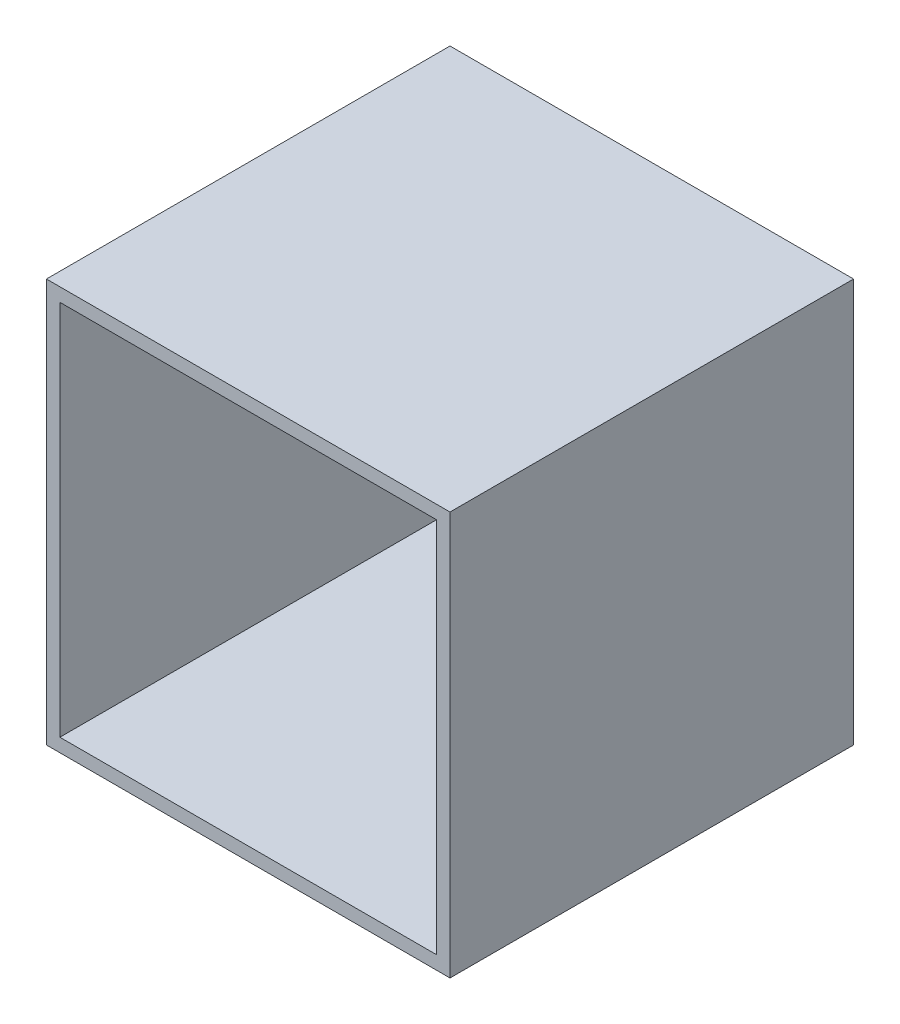
SolidWorks part; units mm, degrees
ref_plane "Front Plane" through (0, 0, 0) normal (0, 0, 1) x (1, 0, 0)
ref_plane "Top Plane" through (0, 0, 0) normal (0, 1, 0) x (1, 0, 0)
ref_plane "Right Plane" through (0, 0, 0) normal (1, 0, 0) x (0, 0, -1)
sketch "Sketch1" plane through (0, 0, 0) normal (0, 1, 0) x (1, 0, 0)
  line L1 (-38.1, -38.1) -> (38.1, -38.1)
  line L2 (-38.1, -38.1) -> (-38.1, 38.1)
  line L3 (-38.1, 38.1) -> (38.1, 38.1)
  line L4 (38.1, -38.1) -> (38.1, 38.1)
  line L5 (-38.1, -38.1) -> (38.1, 38.1) construction
  line L6 (-38.1, 38.1) -> (38.1, -38.1) construction
  point P0 (0, 0)
  dimension "D1" = 76.2
  dimension "D2" = 76.2
extrude "box" add sketch "Sketch1" along normal blind 76.2
shell "hollow it" thickness 2.54 removed face at (0, 38.1, 38.1)
sketch "Sketch2" plane through (0, 0, -38.1) normal (0, 0, -1) x (-1, 0, 0)
  line L0 (-38.1, 76.2) -> (38.1, 76.2) construction
  line L1 (-27.94, 69.85) -> (-20.32, 69.85)
  line L2 (-27.94, 69.85) -> (-27.94, 6.35)
  line L3 (-27.94, 6.35) -> (-20.32, 6.35)
  line L4 (-20.32, 69.85) -> (-20.32, 6.35)
  line L6 (-38.1, 76.2) -> (-38.1, 0) construction
  dimension "D1" = 7.62
  dimension "D2" = 63.5
  dimension "D3" = 6.35
  dimension "D4" = 10.16
extrude "slider track" cut sketch "Sketch2" against normal up to surface (2.54 mm away) up to face at (0, 38.1, -35.56)
sketch "Sketch4" plane through (0, 0, -38.1) normal (0, 0, -1) x (-1, 0, 0)
  line L0 (-38.1, 76.2) -> (38.1, 76.2) construction
  circle A0 centre (0, 57.15) radius 6.35
  dimension "D1" = 12.7
  dimension "D2" = 19.05
extrude "button large ring" cut sketch "Sketch4" against normal blind 1.27
sketch "Sketch5" plane through (0, 0, -36.83) normal (0, 0, -1) x (-1, 0, 0)
  circle A0 centre (0, 57.15) radius 3.556
  circle A1 centre (0, 57.15) radius 6.35 construction
  dimension "D2" = 7.112
  dimension "D1" = 0
extrude "button small hole" cut sketch "Sketch5" against normal blind 1.27
sketch "Sketch6" plane through (0, 0, -38.1) normal (0, 0, -1) x (-1, 0, 0)
  line L0 (-3.2977, 25.4) -> (-3.2977, 31.75)
  line L1 (-3.2977, 31.75) -> (3.0523, 31.75)
  line L2 (3.0523, 31.75) -> (3.0523, 25.4)
  line L3 (3.0523, 25.4) -> (9.4023, 25.4)
  line L4 (9.4023, 25.4) -> (9.4023, 19.05)
  line L5 (9.4023, 19.05) -> (3.0523, 19.05)
  line L6 (3.0523, 19.05) -> (3.0523, 12.7)
  line L7 (3.0523, 12.7) -> (-3.2977, 12.7)
  line L8 (-3.2977, 12.7) -> (-3.2977, 19.05)
  line L9 (-3.2977, 19.05) -> (-9.6477, 19.05)
  line L10 (-9.6477, 19.05) -> (-9.6477, 25.4)
  line L11 (-9.6477, 25.4) -> (-3.2977, 25.4)
  line L12 (-38.1, 0) -> (38.1, 0) construction
  dimension "D1" = 6.35
  dimension "D2" = 6.35
  dimension "D3" = 6.35
  dimension "D4" = 6.35
  dimension "D5" = 6.35
  dimension "D6" = 6.35
  dimension "D7" = 6.35
  dimension "D8" = 6.35
  dimension "D9" = 6.35
  dimension "D10" = 12.7
extrude "dpad large shape" cut sketch "Sketch6" against normal blind 1.27
sketch "Sketch7" plane through (0, 0, -36.83) normal (0, 0, -1) x (-1, 0, 0)
  line L0 (-3.2977, 25.4) -> (-9.6477, 25.4) construction
  line L1 (-9.6477, 25.4) -> (-9.6477, 19.05) construction
  line L2 (3.0523, 12.7) -> (3.0523, 19.05) construction
  line L3 (-3.2977, 12.7) -> (3.0523, 12.7) construction
  line L4 (3.0523, 19.05) -> (9.4023, 19.05) construction
  line L5 (9.4023, 19.05) -> (9.4023, 25.4) construction
  line L6 (3.0523, 25.4) -> (3.0523, 31.75) construction
  line L7 (-3.2977, 31.75) -> (-3.2977, 25.4) construction
  line L8 (3.0523, 31.75) -> (-3.2977, 31.75) construction
  circle A0 centre (-0.1227, 28.575) radius 1.397
  circle A1 centre (6.2273, 22.225) radius 1.397
  circle A2 centre (-0.1227, 15.875) radius 1.397
  circle A3 centre (-6.4727, 22.225) radius 1.397
  point P12 (3.0523, 15.875)
  point P17 (6.2273, 19.05)
  dimension "D3" = 2.794
  dimension "D6" = 2.794
  dimension "D9" = 2.794
  dimension "D13" = 2.794
  dimension "D1" = 3.175
  dimension "D2" = 3.175
  dimension "D4" = 3.175
  dimension "D5" = 3.175
  dimension "D7" = 3.175
  dimension "D8" = 3.175
  dimension "D10" = 3.175
  dimension "D11" = 3.175
  dimension "D12" = 3.175
extrude "dpad tiny holes" cut sketch "Sketch7" against normal blind 1.27
sketch "Sketch8" plane through (0, 0, -38.1) normal (0, 0, -1) x (-1, 0, 0)
  line L0 (38.1, 76.2) -> (38.1, 0) construction
  circle A0 centre (21.336, 43.0507) radius 12.7
  dimension "D1" = 25.4
  dimension "D2" = 16.764
extrude "dial large ring" cut sketch "Sketch8" against normal blind 1.27
ref_point "dial center"
sketch "Sketch9" plane through (0, 0, -36.83) normal (0, 0, -1) x (-1, 0, 0)
  circle A0 centre (21.336, 43.0507) radius 3.81
  dimension "D1" = 7.62
extrude "dial small hole" cut sketch "Sketch9" against normal blind 1.27
